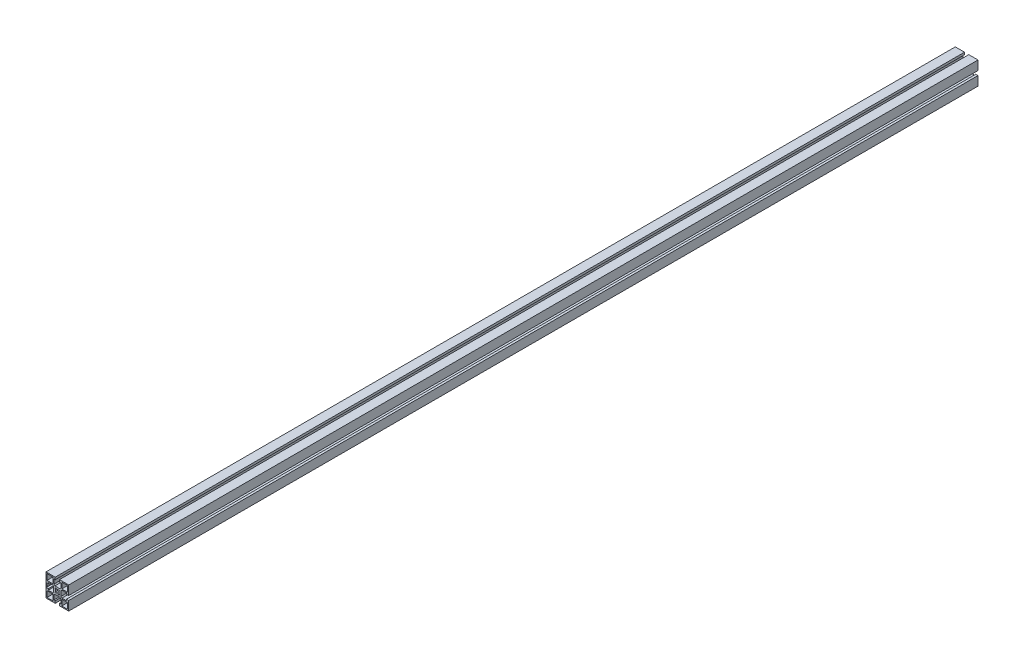
SolidWorks part; units mm, degrees
material "6061 Alloy"
ref_plane "Front Plane" through (0, 0, 0) normal (0, 0, 1) x (1, 0, 0)
ref_plane "Top Plane" through (0, 0, 0) normal (0, 1, 0) x (1, 0, 0)
ref_plane "Right Plane" through (0, 0, 0) normal (1, 0, 0) x (0, 0, -1)
sketch "Sketch1" plane through (0, 0, 0) normal (0, 0, 1) x (1, 0, 0)
  line L0 (-4.2495, 22.1993) -> (-4.2495, 22.4993)
  line L1 (-4.2495, 22.4993) -> (-4.2495, 22.1993)
  line L2 (4.2505, 22.1993) -> (4.2505, 22.4993)
  line L3 (4.2505, 22.4993) -> (4.2505, 22.1993)
  line L4 (-22.1995, 4.2493) -> (-22.4995, 4.2493)
  line L5 (-22.1995, -4.2507) -> (-22.4995, -4.2507)
  line L6 (-4.2495, -22.2007) -> (-4.2495, -22.5007)
  line L7 (4.2505, -22.2007) -> (4.2505, -22.5007)
  line L8 (-22.4995, -22.5007) -> (22.5005, -22.5007)
  line L9 (22.5005, -22.5007) -> (22.5005, 22.4993)
  line L10 (22.5005, 22.4993) -> (-22.4995, 22.4993)
  line L11 (-22.4995, 22.4993) -> (-22.4995, -22.5007)
  line L12 (22.2005, -4.2507) -> (22.5005, -4.2507)
  line L13 (22.2005, 4.2493) -> (22.5005, 4.2493)
  line L24 (-20.4995, -20.5007) -> (-20.4995, -8.8007)
  line L25 (-8.7996, -20.5007) -> (-20.4995, -20.5007)
  line L26 (-8.7996, -8.8007) -> (-8.7996, -20.5007)
  line L27 (-20.4995, -8.8007) -> (-8.7996, -8.8007)
  line L28 (8.8005, -20.5008) -> (8.8005, -8.8008)
  line L29 (20.5005, -20.5008) -> (8.8005, -20.5008)
  line L30 (20.5005, -8.8008) -> (20.5005, -20.5008)
  line L31 (8.8005, -8.8008) -> (20.5005, -8.8008)
  line L32 (20.5006, 8.7993) -> (8.8006, 8.7993)
  line L33 (20.5006, 20.4993) -> (20.5006, 8.7993)
  line L34 (8.8006, 20.4993) -> (20.5006, 20.4993)
  line L35 (8.8006, 8.7993) -> (8.8006, 20.4993)
  line L36 (-8.7995, 20.4993) -> (-8.7995, 8.7993)
  line L37 (-8.7995, 8.7993) -> (-20.4995, 8.7993)
  line L38 (-20.4995, 8.7993) -> (-20.4995, 20.4993)
  line L39 (-20.4995, 20.4993) -> (-8.7995, 20.4993)
  line L54 (-22.1995, -3.9507) -> (-21.7318, -3.483)
  line L55 (-22.1995, -4.2507) -> (-22.1995, -3.9507)
  line L56 (-17.9995, -4.2507) -> (-22.1995, -4.2507)
  line L57 (-17.9995, -6.8007) -> (-17.9995, -4.2507)
  line L58 (-9.1995, -6.8007) -> (-17.9995, -6.8007)
  line L59 (-7.1995, -4.8007) -> (-9.1995, -6.8007)
  line L60 (-7.1995, 4.7993) -> (-7.1995, -4.8007)
  line L61 (-9.1995, 6.7993) -> (-7.1995, 4.7993)
  line L62 (-17.9995, 6.7993) -> (-9.1995, 6.7993)
  line L63 (-17.9995, 4.2493) -> (-17.9995, 6.7993)
  line L64 (-22.1995, 4.2493) -> (-17.9995, 4.2493)
  line L65 (-22.1995, 3.9493) -> (-22.1995, 4.2493)
  line L66 (-21.7317, 3.4815) -> (-22.1995, 3.9493)
  line L67 (-20.9995, -1.7152) -> (-20.9995, 1.7137)
  line L82 (-6.7995, -18.0007) -> (-6.7995, -9.2007)
  line L83 (-4.2495, -18.0007) -> (-6.7995, -18.0007)
  line L84 (-4.2495, -22.2007) -> (-4.2495, -18.0007)
  line L85 (-3.9495, -22.2007) -> (-4.2495, -22.2007)
  line L86 (-3.4817, -21.733) -> (-3.9495, -22.2007)
  line L87 (1.715, -21.0007) -> (-1.7139, -21.0007)
  line L88 (3.9505, -22.2007) -> (3.4828, -21.733)
  line L89 (4.2505, -22.2007) -> (3.9505, -22.2007)
  line L90 (4.2505, -18.0007) -> (4.2505, -22.2007)
  line L91 (6.8005, -18.0007) -> (4.2505, -18.0007)
  line L92 (6.8005, -9.2007) -> (6.8005, -18.0007)
  line L93 (4.8005, -7.2007) -> (6.8005, -9.2007)
  line L94 (-4.7995, -7.2007) -> (4.8005, -7.2007)
  line L95 (-6.7995, -9.2007) -> (-4.7995, -7.2007)
  line L110 (7.2005, -4.8007) -> (7.2005, 4.7993)
  line L111 (9.2005, -6.8007) -> (7.2005, -4.8007)
  line L112 (18.0005, -6.8007) -> (9.2005, -6.8007)
  line L113 (18.0005, -4.2507) -> (18.0005, -6.8007)
  line L114 (22.2005, -4.2507) -> (18.0005, -4.2507)
  line L115 (22.2005, -3.9507) -> (22.2005, -4.2507)
  line L116 (21.7327, -3.4829) -> (22.2005, -3.9507)
  line L117 (21.0005, 1.7138) -> (21.0005, -1.7151)
  line L118 (22.2005, 3.9493) -> (21.7328, 3.4816)
  line L119 (22.2005, 4.2493) -> (22.2005, 3.9493)
  line L120 (18.0005, 4.2493) -> (22.2005, 4.2493)
  line L121 (18.0005, 6.7993) -> (18.0005, 4.2493)
  line L122 (9.2005, 6.7993) -> (18.0005, 6.7993)
  line L123 (7.2005, 4.7993) -> (9.2005, 6.7993)
  line L138 (-4.7995, 7.1993) -> (-6.7995, 9.1993)
  line L139 (4.8005, 7.1993) -> (-4.7995, 7.1993)
  line L140 (6.8005, 9.1993) -> (4.8005, 7.1993)
  line L141 (6.8005, 17.9993) -> (6.8005, 9.1993)
  line L142 (4.2505, 17.9993) -> (6.8005, 17.9993)
  line L143 (4.2505, 22.1993) -> (4.2505, 17.9993)
  line L144 (3.9505, 22.1993) -> (4.2505, 22.1993)
  line L145 (3.4828, 21.7316) -> (3.9505, 22.1993)
  line L146 (-1.7139, 20.9993) -> (1.715, 20.9993)
  line L147 (-3.9495, 22.1993) -> (-3.4817, 21.7315)
  line L148 (-4.2495, 22.1993) -> (-3.9495, 22.1993)
  line L149 (-4.2495, 17.9993) -> (-4.2495, 22.1993)
  line L150 (-6.7995, 17.9993) -> (-4.2495, 17.9993)
  line L151 (-6.7995, 9.1993) -> (-6.7995, 17.9993)
  line L164 (-4.5957, -3.1827) -> (-3.2622, -1.8492)
  line L165 (-3.1815, -4.5969) -> (-4.5957, -3.1827)
  line L166 (-1.848, -3.2635) -> (-3.1815, -4.5969)
  line L167 (3.1825, -4.5969) -> (1.849, -3.2635)
  line L168 (4.5967, -3.1827) -> (3.1825, -4.5969)
  line L169 (3.2633, -1.8492) -> (4.5967, -3.1827)
  line L170 (4.5967, 3.1813) -> (3.2633, 1.8478)
  line L171 (3.1825, 4.5955) -> (4.5967, 3.1813)
  line L172 (1.849, 3.262) -> (3.1825, 4.5955)
  line L173 (-3.1815, 4.5955) -> (-1.848, 3.262)
  line L174 (-4.5957, 3.1813) -> (-3.1815, 4.5955)
  line L175 (-3.2622, 1.8478) -> (-4.5957, 3.1813)
  arc A2 (-21.7318, -3.483) -> (-20.9995, -1.7152) centre (-23.4995, -1.7152) ccw
  arc A3 (-20.9995, 1.7137) -> (-21.7317, 3.4815) centre (-23.4995, 1.7137) ccw
  arc A6 (-1.7139, -21.0007) -> (-3.4817, -21.733) centre (-1.7139, -23.5007) ccw
  arc A7 (3.4828, -21.733) -> (1.715, -21.0007) centre (1.715, -23.5007) ccw
  arc A10 (21.0005, -1.7151) -> (21.7327, -3.4829) centre (23.5005, -1.7151) ccw
  arc A11 (21.7328, 3.4816) -> (21.0005, 1.7138) centre (23.5005, 1.7138) ccw
  arc A14 (1.715, 20.9993) -> (3.4828, 21.7316) centre (1.715, 23.4993) ccw
  arc A15 (-3.4817, 21.7315) -> (-1.7139, 20.9993) centre (-1.7139, 23.4993) ccw
  arc A20 (-1.848, -3.2635) -> (1.849, -3.2635) centre (0.0005, -0.0007) ccw
  arc A21 (3.2633, -1.8492) -> (3.2633, 1.8478) centre (0.0005, -0.0007) ccw
  arc A22 (1.849, 3.262) -> (-1.848, 3.262) centre (0.0005, -0.0007) ccw
  arc A23 (-3.2622, 1.8478) -> (-3.2622, -1.8492) centre (0.0005, -0.0007) ccw
extrude "Boss-Extrude1" add sketch "Sketch1" along normal blind 1803.4 contours L138 L151 L150 L149 L0 L10 L11 L4 L64 L63 L62 L61 L60 L59 L58 L57 L56 L5 L8 L6 L84 L83 L82 L95 L94 L93 L92 L91 L90 L7 L9 L12 L114 L113 L112 L111 L110 L123 L122 L121 L120 L13 L2 L143 L142 L141 L140 | L147 A15 L146 A14 L145 L144 L2 L10 L0 L148 | L67 A3 L66 L65 L4 L11 L5 L55 L54 A2 region at (-4.8859, 20.0993, 0) region at (0.0005, 21.8242, 0) region at (-21.8244, -0.0007, 0)
extrude "Cut-Extrude1" cut sketch "Sketch1<4>" along normal up to next contours L147 A15 L146 A14 L145 L144 L2 L10 L0 L148 region at (0.0005, 21.8242, 0)
sketch "Sketch1<4>" plane through (0, 0, 0) normal (0, 0, 1) x (1, 0, 0) same geometry as "Sketch1"
